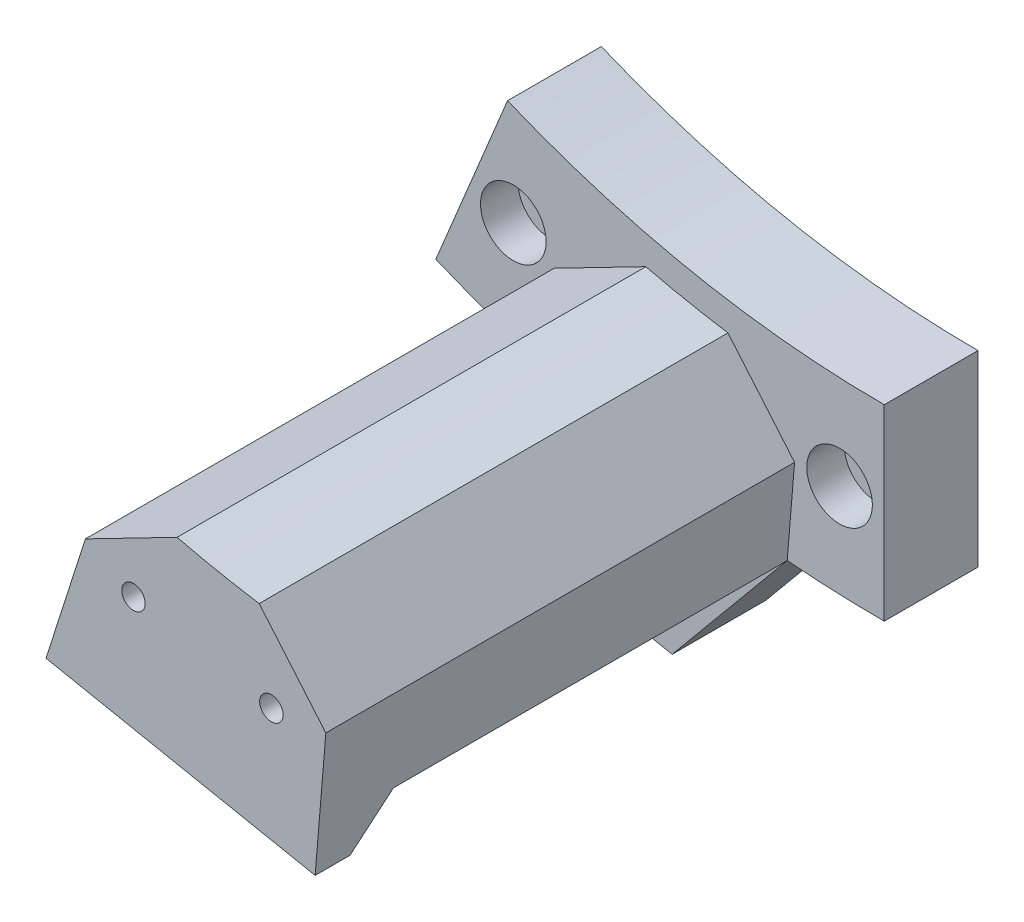
SolidWorks part; units mm, degrees
ref_plane "Plan de face" through (0, 0, 0) normal (0, 0, 1) x (1, 0, 0)
ref_plane "Plan de dessus" through (0, 0, 0) normal (0, 1, 0) x (1, 0, 0)
ref_plane "Plan de droite" through (0, 0, 0) normal (1, 0, 0) x (0, 0, -1)
sketch "Esquisse1" plane through (0, 0, 0) normal (0, 0, 1) x (1, 0, 0)
  line L0 (0, 0) -> (0, -125) construction
  line L1 (0, 0) -> (-47.8354, -115.4849) construction
  line L2 (-40.1818, -97.0074) -> (-47.8354, -115.4849)
  line L3 (0, -105) -> (0, -125)
  arc A0 (0, -125) -> (-47.8354, -115.4849) centre (0, 0) cw
  arc A1 (0, -105) -> (-40.1818, -97.0074) centre (0, 0) cw
  dimension "D2" = 125
  dimension "D3" = 105
  dimension "D1" = 22.5
extrude "Boss.-Extru.1" add sketch "Esquisse1" along normal blind 10
sketch "Esquisse2" plane through (0, 0, 10) normal (0, 0, 1) x (1, 0, 0)
  line L0 (0, 0) -> (-24.3863, -122.5982) construction
  line L1 (0, 0) -> (-10.351, -124.5707) construction
  line L2 (0, 0) -> (-38.108, -119.0495) construction
  line L3 (-32.9253, -102.8587) -> (-38.108, -119.0495)
  line L4 (-8.9433, -107.6291) -> (-10.351, -124.5707)
  arc A0 (-47.8354, -115.4849) -> (0, -125) centre (0, 0) ccw construction
  arc A1 (-10.351, -124.5707) -> (-38.108, -119.0495) centre (0, 0) cw
  arc A2 (-8.9433, -107.6291) -> (-32.9253, -102.8587) centre (0, 0) cw
  arc A3 (-40.1818, -97.0074) -> (0, -105) centre (0, 0) ccw construction
  point P10 (-24.3863, -122.5982)
  dimension "D1" = 3
  dimension "D2" = 13
extrude "Boss.-Extru.2" add sketch "Esquisse2" along normal blind 48
sketch "Esquisse4" plane through (0, 0, 58) normal (0, 0, 1) x (1, 0, 0)
  line L0 (-39.4132, -123.1267) -> (-10.7055, -128.837)
  line L1 (-10.7055, -128.837) -> (-8.9433, -107.6291)
  line L2 (-32.9253, -102.8587) -> (-39.4132, -123.1267)
  line L3 (-32.9253, -102.8587) -> (-38.108, -119.0495) construction
  line L4 (-10.351, -124.5707) -> (-8.9433, -107.6291) construction
  arc A0 (-32.9253, -102.8587) -> (-8.9433, -107.6291) centre (0, 0) ccw construction
  arc A1 (-32.9253, -102.8587) -> (-8.9433, -107.6291) centre (0, 0) ccw
  arc A2 (-38.108, -119.0495) -> (-10.351, -124.5707) centre (0, 0) ccw construction
  point P14 (-24.3863, -122.5982)
  dimension "D1" = 3.45
extrude "Boss.-Extru.3" add sketch "Esquisse4" along normal blind 2
chamfer "Chanfrein1" distance 6 angle 45 1 edges at (-24.3863, -122.5982, 58)
sketch "Esquisse5" plane through (0, 0, 10) normal (0, 0, 1) x (1, 0, 0)
  line L0 (0, 0) -> (-43.0087, -117.368) construction
  line L1 (0, 0) -> (-5.18, -124.8926) construction
  line L2 (-43.0087, -117.368) -> (-36.1273, -98.5891) construction
  line L3 (0, -125) -> (0, -105) construction
  line L4 (-40.1818, -97.0074) -> (-47.8354, -115.4849) construction
  arc A0 (-47.8354, -115.4849) -> (-38.108, -119.0495) centre (0, 0) ccw construction
  arc A1 (-10.351, -124.5707) -> (0, -125) centre (0, 0) ccw construction
  arc A2 (-40.1818, -97.0074) -> (0, -105) centre (0, 0) ccw construction
  arc A3 (0, -115) -> (-44.0086, -106.2461) centre (0, 0) cw construction
  circle A4 centre (-4.7656, -114.9012) radius 1.75
  circle A5 centre (-39.568, -107.9786) radius 1.75
  point P20 (-39.568, -107.9786)
  dimension "D1" = 3.5
extrude "Enlèv. mat.-Extru.1" cut sketch "Esquisse5" against normal up to next
sketch "Esquisse6" plane through (0, 0, 10) normal (0, 0, 1) x (1, 0, 0)
  circle A0 centre (-39.568, -107.9786) radius 3.5
  circle A1 centre (-4.7656, -114.9012) radius 3.5
  dimension "D1" = 7
extrude "Enlèv. mat.-Extru.2" cut sketch "Esquisse6" against normal blind 4
chamfer "Chanfrein2" distance 7.5 angle 45 2 edges at (-8.9433, -107.6291, 35) (-32.9253, -102.8587, 35)
sketch "Esquisse7" plane through (0, 0, 60) normal (0, 0, 1) x (1, 0, 0)
  line L0 (-21.0698, -105.9248) -> (-24.3863, -122.5982) construction
  line L1 (-30.0839, -112.7983) -> (-15.3721, -115.7247) construction
  arc A0 (-38.108, -119.0495) -> (-10.351, -124.5707) centre (0, 0) ccw construction
  arc A1 (-38.108, -119.0495) -> (-10.351, -124.5707) centre (0, 0) ccw construction
  arc A2 (-25.4295, -104.9635) -> (-16.674, -106.7051) centre (0, 0) ccw construction
  circle A3 centre (-30.0839, -112.7983) radius 1.25
  circle A4 centre (-15.3721, -115.7247) radius 1.25
  point P12 (-22.728, -114.2615)
  point P13 (-22.728, -114.2615)
  dimension "D1" = 2.5
  dimension "D2" = 15
extrude "Enlèv. mat.-Extru.3" cut sketch "Esquisse7" against normal blind 10
sketch "Esquisse8" plane through (0, 0, 0) normal (0, 0, -1) x (-1, 0, 0)
  line L0 (24.3863, -122.5982) -> (0, 0) construction
  line L2 (24.3863, -122.5982) -> (27.5468, -138.4869) construction
  line L3 (32.4334, -137.4246) -> (38.108, -119.0495)
  line L5 (32.4334, -137.4246) -> (22.6256, -139.3755)
  line L7 (22.6256, -139.3755) -> (10.351, -124.5707)
  line L8 (35.2118, -110.0017) -> (38.108, -119.0495) construction
  line L9 (35.2118, -110.0017) -> (38.108, -119.0495) construction
  arc A1 (38.108, -119.0495) -> (10.351, -124.5707) centre (0, 0) cw
  arc A5 (0, -125) -> (47.8354, -115.4849) centre (0, 0) ccw construction
  dimension "D2" = 141.2
  dimension "D3" = 10
extrude "Boss.-Extru.4" add sketch "Esquisse8" against normal blind 10
sketch "Esquisse9" plane through (-27.5295, -138.4, 0) normal (-0.1951, -0.9808, 0) x (0.9808, -0.1951, 0)
  line L0 (5, 10) -> (-5, 0) construction
  circle A0 centre (0, 5) radius 2.75
  dimension "D1" = 5.5
extrude "Enlèv. mat.-Extru.4" cut sketch "Esquisse9" against normal blind 2
